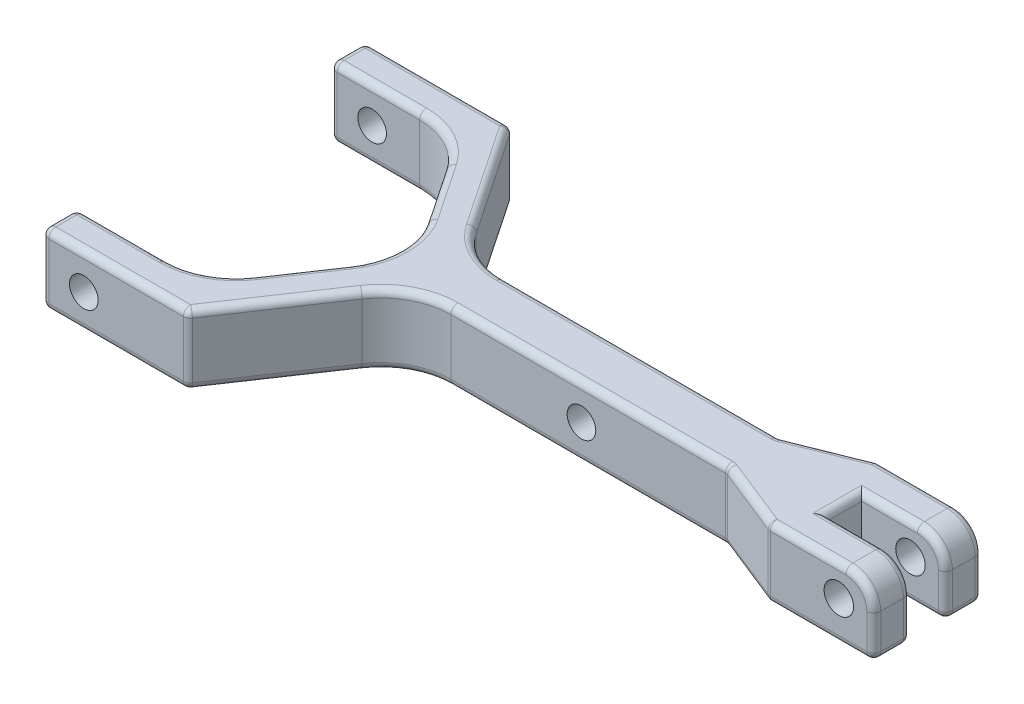
SolidWorks part; units mm, degrees
ref_plane "Front" through (0, 0, 0) normal (0, 0, 1) x (1, 0, 0)
ref_plane "Top" through (0, 0, 0) normal (0, 1, 0) x (1, 0, 0)
ref_plane "Right" through (0, 0, 0) normal (1, 0, 0) x (0, 0, -1)
sketch "Esquisse1" plane through (0, 0, 0) normal (0, 0, 1) x (1, 0, 0)
  line L1 (-6.35, 6.35) -> (6.35, 6.35)
  line L2 (-6.35, 6.35) -> (-6.35, -6.35)
  line L3 (-6.35, -6.35) -> (6.35, -6.35)
  line L4 (6.35, 6.35) -> (6.35, -6.35)
  line L5 (-6.35, 6.35) -> (6.35, -6.35) construction
  line L6 (-6.35, -6.35) -> (6.35, 6.35) construction
  point P0 (0, 0)
  dimension "D1" = 12.7
  dimension "D2" = 12.7
extrude "Boss.-Extru.1" add sketch "Esquisse1" along normal mid plane 9.525
sketch "Esquisse2" plane through (0, 0, 4.7625) normal (0, 0, 1) x (1, 0, 0)
  circle A0 centre (0, 0) radius 2.6
  dimension "D1" = 5.2
extrude "Enlèv. mat.-Extru.1" cut sketch "Esquisse2" against normal through all
sketch "Esquisse4" plane through (6.35, 0, 0) normal (1, 0, 0) x (0, 0, -1)
  line L1 (-4.7625, 6.35) -> (4.7625, 6.35)
  line L2 (-4.7625, 6.35) -> (-4.7625, -6.35)
  line L3 (-4.7625, -6.35) -> (4.7625, -6.35)
  line L4 (4.7625, 6.35) -> (4.7625, -6.35)
  line L5 (-4.7625, 6.35) -> (4.7625, -6.35) construction
  line L6 (-4.7625, -6.35) -> (4.7625, 6.35) construction
extrude "Boss.-Extru.3" add sketch "Esquisse4" along normal blind 51.8414
sketch "Esquisse6" plane through (0, 6.35, 0) normal (0, 1, 0) x (1, 0, 0)
  line L0 (58.1914, 4.7625) -> (58.1914, -4.7625) construction
  line L1 (58.1914, 3.175) -> (42.9514, 3.175)
  line L2 (58.1914, 3.175) -> (58.1914, -3.175)
  line L3 (58.1914, -3.175) -> (42.9514, -3.175)
  line L4 (42.9514, 3.175) -> (42.9514, -3.175)
  line L7 (42.9514, 3.175) -> (58.1914, -3.175) construction
  line L8 (58.1914, 3.175) -> (42.9514, -3.175) construction
  line L9 (58.1914, 4.7625) -> (-6.35, 4.7625) construction
  point P6 (50.5714, 0)
  dimension "D1" = 6.35
  dimension "D2" = 4.7625
  dimension "D3" = 15.24
extrude "Enlèv. mat.-Extru.3" cut sketch "Esquisse6" against normal through all
sketch "Esquisse7" plane through (-6.35, 0, 0) normal (-1, 0, 0) x (0, 0, 1)
  line L1 (-4.7625, 6.35) -> (4.7625, 6.35)
  line L2 (-4.7625, 6.35) -> (-4.7625, -6.35)
  line L3 (-4.7625, -6.35) -> (4.7625, -6.35)
  line L4 (4.7625, 6.35) -> (4.7625, -6.35)
extrude "Boss.-Extru.4" add sketch "Esquisse7" along normal blind 28.575
sketch "Esquisse8" plane through (0, 6.35, 0) normal (0, 1, 0) x (1, 0, 0)
  line L0 (-30.4762, 4.7625) -> (-47.0387, 29.3687)
  line L1 (-47.0387, 29.3687) -> (-73.4314, 29.3687)
  line L2 (-73.4314, 29.3687) -> (-73.4314, 23.0187)
  line L3 (-73.4314, 23.0187) -> (-50.419, 23.0187)
  line L4 (-50.419, 23.0187) -> (-34.925, 0)
  line L5 (-34.925, -4.7625) -> (-34.925, 4.7625) construction
  line L6 (-34.925, 0) -> (-50.419, -23.0187)
  line L7 (-50.419, -23.0187) -> (-73.4314, -23.0188)
  line L8 (-73.4314, -23.0188) -> (-73.4314, -29.3687)
  line L9 (-73.4314, -29.3687) -> (-47.0387, -29.3687)
  line L10 (-47.0387, -29.3687) -> (-30.4762, -4.7625)
  line L11 (58.1914, -4.7625) -> (-34.925, -4.7625) construction
  line L12 (58.1914, 4.7625) -> (-34.925, 4.7625) construction
  line L13 (-34.925, 0) -> (-91.3633, 0) construction
  line L14 (-30.4762, -4.7625) -> (-30.4762, 4.7625)
  dimension "D1" = 6.35
  dimension "D2" = 6.35
  dimension "D3" = 6.35
  dimension "D4" = 6.35
  dimension "D5" = 46.0375
  dimension "D6" = 23.0187
  dimension "D7" = 23.0124
  dimension "D8" = 15.494
  dimension "D9" = 15.494
extrude "Boss.-Extru.5" add sketch "Esquisse8" against normal blind 12.7
sketch "Esquisse10" plane through (0, 0, 29.3687) normal (0, 0, 1) x (1, 0, 0)
  line L0 (-73.4314, 6.35) -> (-47.0387, 6.35) construction
  line L1 (-73.4314, -6.35) -> (-73.4314, 6.35) construction
  circle A0 centre (-65.8153, -0.1031) radius 2.6
  dimension "D1" = 6.4531
  dimension "D3" = 5.2
  dimension "D2" = 7.6161
extrude "Enlèv. mat.-Extru.4" cut sketch "Esquisse10" against normal through all
sketch "Esquisse11" plane through (0, 6.35, 0) normal (0, 1, 0) x (1, 0, 0)
  line L1 (58.1914, 4.7625) -> (-30.4762, 4.7625) construction
  line L2 (58.1914, 9.8425) -> (58.1914, 4.7625)
  line L3 (58.1914, 4.7625) -> (26.4414, 4.7625)
  line L4 (26.4414, 4.7625) -> (39.1414, 9.8425)
  line L5 (39.1414, 9.8425) -> (58.1914, 9.8425)
  line L6 (58.1914, -4.7625) -> (-30.4762, -4.7625) construction
  line L7 (26.4414, -4.7625) -> (39.1414, -9.8425)
  line L8 (39.1414, -9.8425) -> (58.1914, -9.8425)
  line L9 (58.1914, -9.8425) -> (58.1914, -4.7625)
  line L10 (58.1914, -4.7625) -> (26.4414, -4.7625)
  dimension "D2" = 5.08
  dimension "D3" = 31.75
  dimension "D4" = 19.05
extrude "Boss.-Extru.6" add sketch "Esquisse11" against normal blind 12.7
sketch "Esquisse5" plane through (0, 0, 9.8425) normal (0, 0, 1) x (1, 0, 0)
  line L0 (58.1914, 6.35) -> (58.1914, -6.35) construction
  line L1 (-30.4762, -6.35) -> (26.4414, -6.35) construction
  circle A0 centre (51.8414, 0.762) radius 2.6797
  dimension "D1" = 5.3594
  dimension "D2" = 6.35
  dimension "D3" = 7.112
extrude "Enlèv. mat.-Extru.2" cut sketch "Esquisse5" against normal through all
fillet "Congé1" radius 12.7 5 edges at (-50.419, 0, -23.0187) (-50.419, 0, 23.0187) (-34.925, 0, 0) (-30.4762, 0, -4.7625) (-30.4762, 0, 4.7625)
fillet "Congé2" radius 1.27 64 edges at (-40.645, 6.35, 19.8698) (-29.6833, 6.35, 6.2519) (1.3629, 6.35, 4.7625) (-40.645, -6.35, -19.8698) (-29.6833, -6.35, -6.2519) (-65.3055, -6.35, -23.0187) (-51.2119, -6.35, -21.5293) (-43.1712, -6.35, -12.2509) (-37.534, -6.35, 0) (-43.1712, -6.35, 12.2509) (-51.2119, -6.35, 21.5293) (1.3629, -6.35, 4.7625) (-29.6833, -6.35, 6.2519) (-40.645, 6.35, -19.8698) (-65.3055, 6.35, -23.0187) (-51.2119, 6.35, -21.5293) (-43.1712, 6.35, -12.2509) (-37.534, 6.35, 0) (-43.1712, 6.35, 12.2509) (-51.2119, 6.35, 21.5293) (1.3629, 6.35, -4.7625) (1.3629, -6.35, -4.7625) (58.1914, 0, -3.175) (58.1914, 0, 3.175) (58.1914, -6.35, 6.5088) (58.1914, -6.35, -6.5087) (-47.0387, 0, -29.3687) (-60.2351, -6.35, -29.3687) (-60.2351, 6.35, -29.3687) (-73.4314, -6.35, -26.1937) (-73.4314, 0, -29.3687) (-73.4314, 6.35, -26.1937) (-65.3055, -6.35, 23.0187) (-73.4314, -6.35, 26.1938) (-73.4314, 0, 23.0188) (-68.4153, -0.1031, 23.0187) (-73.4314, 0, 29.3687) (-40.645, -6.35, 19.8698) (-60.2351, -6.35, 29.3687) (-47.0387, 0, 29.3687) (-29.6833, 6.35, -6.2519) (-65.3055, 6.35, 23.0187) (-73.4314, 6.35, 26.1938) (-60.2351, 6.35, 29.3687) (32.7914, -6.35, -7.3025) (32.7914, 6.35, -7.3025) (26.4414, 0, -4.7625) (32.7914, -6.35, 7.3025) (50.5714, 6.35, -3.175) (42.9514, 6.35, 0) (50.5714, 6.35, 3.175) (48.6664, 6.35, 9.8425) (32.7914, 6.35, 7.3025) (48.6664, 6.35, -9.8425) (48.6664, -6.35, 9.8425) (42.9514, -6.35, 0) (50.5714, -6.35, 3.175) (50.5714, -6.35, -3.175) (48.6664, -6.35, -9.8425) (58.1914, 0, -9.8425) (58.1914, 0, 9.8425) (39.1414, 0, 9.8425) (26.4414, 0, 4.7625) (-73.4314, 0, -23.0187)
fillet "Congé3" radius 5.08 6 edges at (57.8194, 5.978, -3.547) (57.8194, 5.978, -9.4705) (57.8194, 5.978, 9.4705) (57.8194, 5.978, 3.547) (58.1914, 6.35, 6.5088) (58.1914, 6.35, -6.5087)
